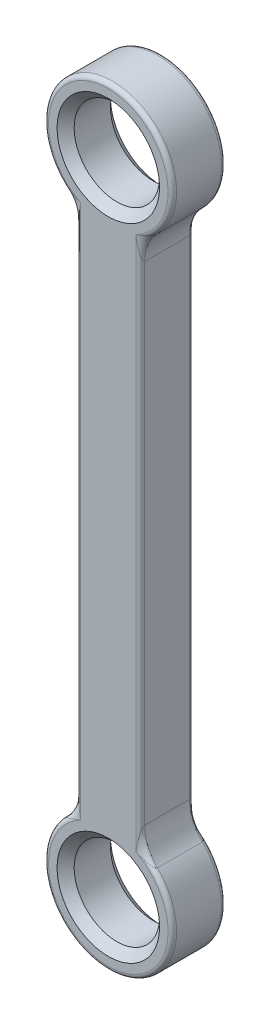
SolidWorks part; units mm, degrees
ref_plane "Ön Düzlem" through (0, 0, 0) normal (0, 0, 1) x (1, 0, 0)
ref_plane "Üst Düzlem" through (0, 0, 0) normal (0, 1, 0) x (1, 0, 0)
ref_plane "Sağ Düzlem" through (0, 0, 0) normal (1, 0, 0) x (0, 0, -1)
sketch "Çizim1" plane through (0, 0, 0) normal (0, 0, 1) x (1, 0, 0)
  line L0 (0, -75) -> (0, 75) construction
  line L1 (-7.5, 0) -> (7.5, 0) construction
  line L2 (-7.5, 62.0096) -> (-7.5, -62.0096)
  line L3 (7.5, 62.0096) -> (7.5, -62.0096)
  circle A0 centre (0, -75) radius 10
  arc A1 (-7.5, -62.0096) -> (7.5, -62.0096) centre (0, -75) ccw
  arc A2 (-7.5, 62.0096) -> (7.5, 62.0096) centre (0, 75) cw
  circle A3 centre (0, 75) radius 10
  point P5 (0, 0)
  point P10 (-7.5, 0)
  point P12 (7.5, 0)
  dimension "D3" = 15
  dimension "D4" = 20
  dimension "D1" = 150
  dimension "D2" = 15
extrude "Yükseklik-Ekstrüzyon1" add sketch "Çizim1" along normal blind 12.5
chamfer "Pah1" distance 2 angle 45 4 edges at (10, -75, 12.5) (10, -75, 0) (-10, 75, 0) (-10, 75, 12.5)
fillet "Radyus1" radius 1 8 edges at (-7.5, 0, 0) (0, 90, 12.5) (0, 90, 0) (0, -90, 0) (7.5, 0, 0) (7.5, 0, 12.5) (0, -90, 12.5) (-7.5, 0, 12.5)
fillet "Radyus2" radius 10 12 edges at (7.3273, 62.1097, 12.0618) (7.3273, 62.1097, 0.4382) (-7.3273, 62.1097, 12.0618) (-7.3273, 62.1097, 0.4382) (-7.3273, -62.1097, 12.0618) (-7.3273, -62.1097, 0.4382) (7.3273, -62.1097, 12.0618) (7.3273, -62.1097, 0.4382) (7.5, 62.0096, 6.25) (-7.5, 62.0096, 6.25) (-7.5, -62.0096, 6.25) (7.5, -62.0096, 6.25)
